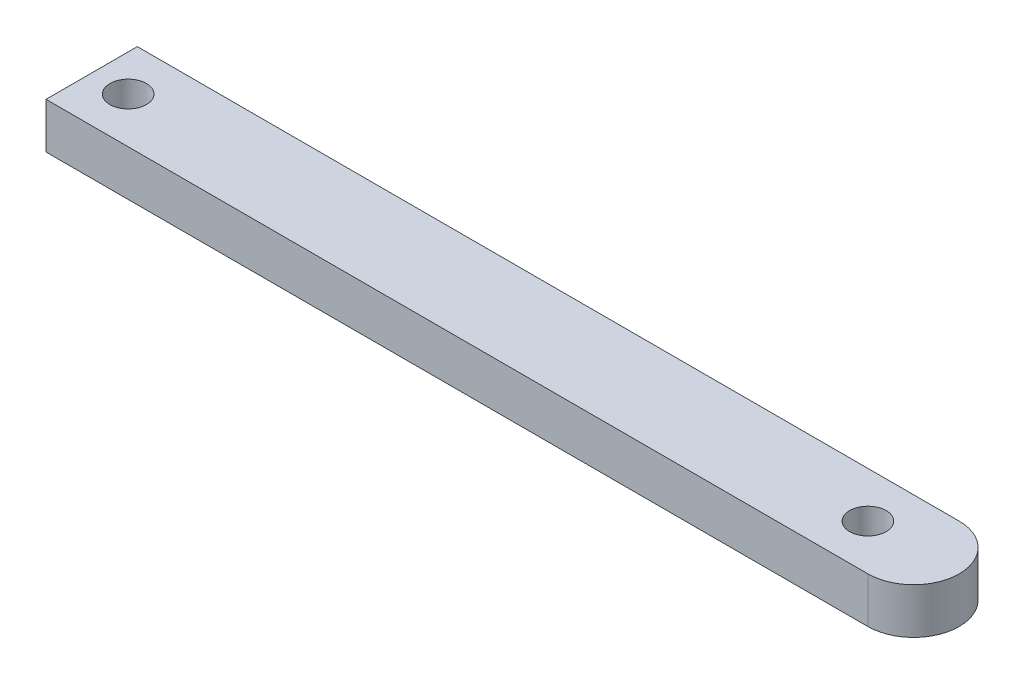
SolidWorks part; units mm, degrees
ref_plane "Front" through (0, 0, 0) normal (0, 0, 1) x (1, 0, 0)
ref_plane "Top" through (0, 0, 0) normal (0, 1, 0) x (1, 0, 0)
ref_plane "Right" through (0, 0, 0) normal (1, 0, 0) x (0, 0, -1)
sketch "Sketch1" plane through (0, 0, 0) normal (0, 1, 0) x (1, 0, 0)
  line L0 (90, 5) -> (80, 5) construction
  line L1 (0, 0) -> (80, 0)
  line L2 (0, 0) -> (0, 10)
  line L3 (0, 10) -> (80, 10)
  line L4 (80, 0) -> (80, 10)
  line L5 (90, 0) -> (80, 0)
  line L6 (90, 10) -> (80, 10)
  line L10 (0, 5) -> (4, 5)
  arc A0 (90, 0) -> (90, 10) centre (90, 5) ccw
  arc A1 (80, 10) -> (80, 0) centre (80, 5) ccw
  circle A4 centre (4, 5) radius 2
  circle A5 centre (12, 5) radius 2
  circle A6 centre (85, 5) radius 2
  point P7 (85, 5)
  dimension "D1" = 80
  dimension "D2" = 10
  dimension "D3" = 10
  dimension "D4" = 10
  dimension "D6" = 2
extrude "Boss-Extrude1" add sketch "Sketch1" along normal blind 5 contours A4 L2 L1 A1 L3 A5 | L4 A1 | L4 L5 A0 L6 | A5 region at (39.0712, 0, -5) region at (77.8779, 0, -5) region at (87.2074, 0, -5) region at (12, 0, -5)
